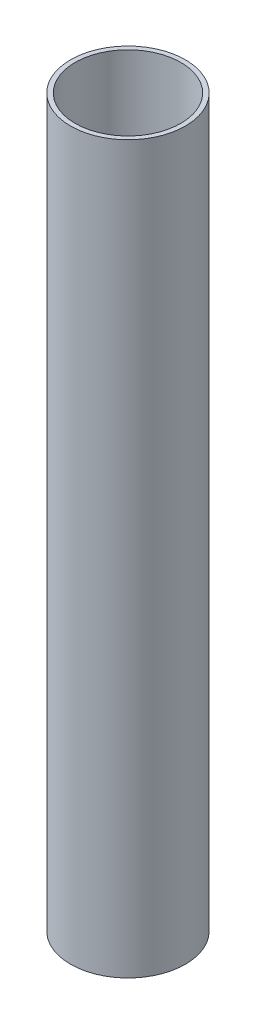
SolidWorks part; units mm, degrees
material "ПВХ 0.007 Смягченный"
ref_plane "Спереди" through (0, 0, 0) normal (0, 0, 1) x (1, 0, 0)
ref_plane "Сверху" through (0, 0, 0) normal (0, 1, 0) x (1, 0, 0)
ref_plane "Справа" through (0, 0, 0) normal (1, 0, 0) x (0, 0, -1)
sketch "Эскиз1" plane through (0, 0, 0) normal (0, 1, 0) x (1, 0, 0)
  circle A0 centre (0, 0) radius 25
  circle A1 centre (0, 0) radius 23
  dimension "ExDBody" = 50
  dimension "InDBody" = 46
extrude "Бобышка-Вытянуть1" add sketch "Эскиз1" along normal blind 316
